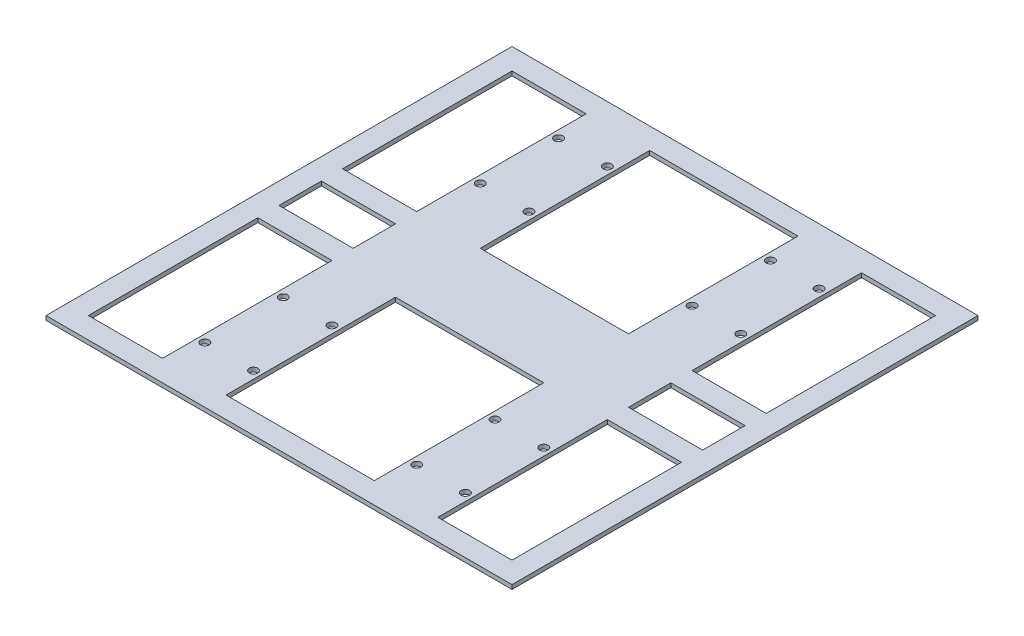
SolidWorks part; units mm, degrees
ref_plane "Спереди" through (0, 0, 0) normal (0, 0, 1) x (1, 0, 0)
ref_plane "Сверху" through (0, 0, 0) normal (0, 1, 0) x (1, 0, 0)
ref_plane "Справа" through (0, 0, 0) normal (1, 0, 0) x (0, 0, -1)
sketch "Эскиз2" plane through (0, 0, 0) normal (0, 1, 0) x (1, 0, 0)
  line L0 (10, 210) -> (10, 130)
  line L1 (0, 0) -> (220, 0)
  line L2 (0, 0) -> (0, 220)
  line L3 (0, 220) -> (220, 220)
  line L4 (220, 0) -> (220, 220)
  line L5 (75, 210) -> (145, 210)
  line L6 (75, 210) -> (75, 130)
  line L7 (75, 130) -> (145, 130)
  line L8 (145, 210) -> (145, 130)
  line L9 (175, 210) -> (210, 210)
  line L10 (10, 130) -> (45, 130)
  line L11 (175, 10) -> (210, 10)
  line L12 (45, 130) -> (45, 210)
  line L13 (75, 90) -> (145, 90)
  line L14 (75, 90) -> (75, 10)
  line L15 (75, 10) -> (145, 10)
  line L16 (145, 90) -> (145, 10)
  line L17 (45, 10) -> (10, 10)
  line L18 (10, 10) -> (10, 90)
  line L19 (45, 210) -> (10, 210)
  line L20 (10, 90) -> (45, 90)
  line L21 (45, 90) -> (45, 10)
  line L22 (175, 210) -> (175, 130)
  line L23 (175, 130) -> (210, 130)
  line L24 (210, 130) -> (210, 210)
  line L25 (175, 90) -> (210, 90)
  line L26 (210, 90) -> (210, 10)
  line L27 (175, 10) -> (175, 90)
  line L29 (10, 120) -> (45, 120)
  line L30 (10, 120) -> (10, 100)
  line L31 (10, 100) -> (45, 100)
  line L32 (45, 120) -> (45, 100)
  line L33 (210, 120) -> (175, 120)
  line L34 (210, 120) -> (210, 100)
  line L35 (210, 100) -> (175, 100)
  line L36 (175, 120) -> (175, 100)
  point P21 (110, 90)
  dimension "D1" = 220
  dimension "D2" = 220
  dimension "D3" = 10
  dimension "D4" = 70
  dimension "D5" = 30
  dimension "D6" = 30
  dimension "D7" = 35
  dimension "D8" = 35
  dimension "D9" = 35
  dimension "D10" = 35
  dimension "D11" = 70
  dimension "D12" = 10
  dimension "D13" = 40
  dimension "D14" = 10
  dimension "D15" = 10
  dimension "D16" = 10
  dimension "D17" = 10
  dimension "D18" = 10
  dimension "D19" = 10
  dimension "D20" = 80
  dimension "D21" = 80
  dimension "D22" = 10
  dimension "D23" = 40
  dimension "D24" = 10
  dimension "D25" = 10
  dimension "D26" = 10
  dimension "D27" = 35
  dimension "D28" = 35
  dimension "D29" = 10
  dimension "D30" = 10
  dimension "D31" = 10
extrude "Бобышка-Вытянуть1" add sketch "Эскиз2" along normal blind 2
sketch "Эскиз3" plane through (0, 2, 0) normal (0, 1, 0) x (1, 0, 0)
  line L0 (171.5, 26.5) -> (171.5, 63.5) construction
  line L1 (171.5, 63.5) -> (148.5, 63.5) construction
  line L2 (148.5, 63.5) -> (148.5, 26.5) construction
  line L3 (148.5, 26.5) -> (171.5, 26.5) construction
  line L4 (71.5, 26.5) -> (48.5, 26.5) construction
  line L5 (48.5, 26.5) -> (48.5, 63.5) construction
  line L6 (48.5, 63.5) -> (71.5, 63.5) construction
  line L7 (71.5, 63.5) -> (71.5, 26.5) construction
  line L10 (60, 26.5) -> (60, 63.5) construction
  line L11 (75, 90) -> (75, 10) construction
  line L12 (45, 10) -> (45, 90) construction
  line L13 (160, 26.5) -> (160, 63.5) construction
  line L14 (175, 90) -> (175, 10) construction
  line L15 (145, 10) -> (145, 90) construction
  line L16 (171.5, 45) -> (148.5, 45) construction
  line L17 (71.5, 45) -> (48.5, 45) construction
  line L18 (171.5, 156.5) -> (148.5, 156.5) construction
  line L19 (148.5, 156.5) -> (148.5, 193.5) construction
  line L20 (148.5, 193.5) -> (171.5, 193.5) construction
  line L21 (171.5, 193.5) -> (171.5, 156.5) construction
  line L22 (171.5, 175) -> (148.5, 175) construction
  line L23 (160, 156.5) -> (160, 193.5) construction
  line L24 (71.5, 156.5) -> (48.5, 156.5) construction
  line L25 (48.5, 156.5) -> (48.5, 193.5) construction
  line L26 (48.5, 193.5) -> (71.5, 193.5) construction
  line L27 (71.5, 193.5) -> (71.5, 156.5) construction
  line L28 (71.5, 175) -> (48.5, 175) construction
  line L29 (60, 156.5) -> (60, 193.5) construction
  line L30 (145, 130) -> (145, 210) construction
  line L31 (175, 210) -> (175, 130) construction
  line L32 (75, 210) -> (75, 130) construction
  line L33 (45, 130) -> (45, 210) construction
  line L34 (220, 110) -> (0, 110) construction
  line L35 (220, 0) -> (220, 220) construction
  line L36 (0, 220) -> (0, 0) construction
  circle A0 centre (171.5, 26.5) radius 2
  circle A1 centre (148.5, 26.5) radius 2
  circle A2 centre (71.5, 26.5) radius 2
  circle A3 centre (48.5, 26.5) radius 2
  circle A4 centre (48.5, 63.5) radius 2
  circle A5 centre (71.5, 63.5) radius 2
  circle A6 centre (148.5, 63.5) radius 2
  circle A7 centre (171.5, 63.5) radius 2
  circle A8 centre (171.5, 156.5) radius 2
  circle A9 centre (148.5, 156.5) radius 2
  circle A10 centre (148.5, 193.5) radius 2
  circle A11 centre (171.5, 193.5) radius 2
  circle A12 centre (71.5, 193.5) radius 2
  circle A13 centre (71.5, 156.5) radius 2
  circle A14 centre (48.5, 156.5) radius 2
  circle A15 centre (48.5, 193.5) radius 2
  point P22 (60, 63.5)
  dimension "D1" = 4
  dimension "D2" = 37
  dimension "D3" = 37
  dimension "D4" = 23
  dimension "D5" = 23
  dimension "D6" = 130
  dimension "D7" = 37
  dimension "D8" = 23
  dimension "D9" = 37
extrude "Вырез-Вытянуть1" cut sketch "Эскиз3" against normal up to surface (2 mm away) up to face at (110, 0, -110)
